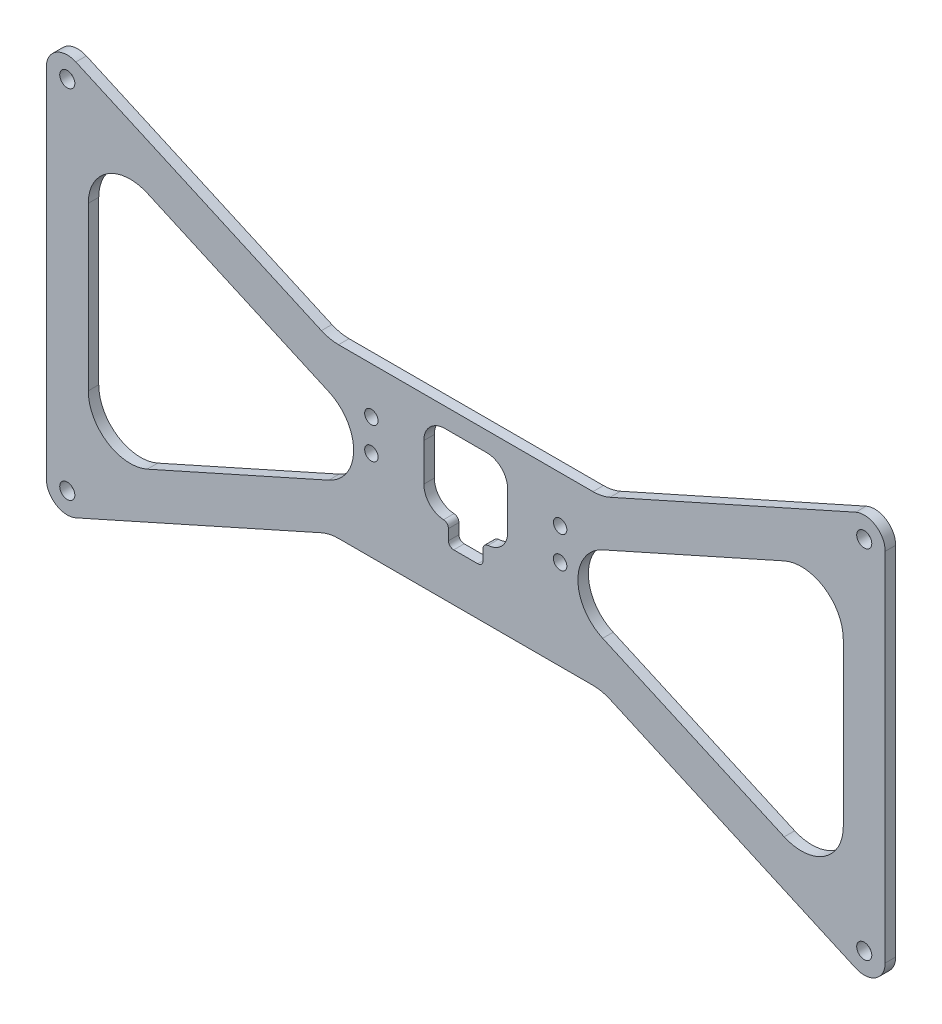
SolidWorks part; units mm, degrees
ref_plane "Front Plane" through (0, 0, 0) normal (0, 0, 1) x (1, 0, 0)
ref_plane "Top Plane" through (0, 0, 0) normal (0, 1, 0) x (1, 0, 0)
ref_plane "Right Plane" through (0, 0, 0) normal (1, 0, 0) x (0, 0, -1)
sketch "Sketch1" plane through (0, 0, 0) normal (0, 0, 1) x (1, 0, 0)
  line L0 (-120.65, -53.975) -> (120.65, 53.975) construction
  line L3 (-114.3, -44.1777) -> (-15.5498, 0)
  line L10 (-118.0569, -59.7714) -> (-41.2267, -25.4)
  line L11 (-120.65, 53.975) -> (120.65, -53.975) construction
  line L12 (-118.0569, 59.7714) -> (-41.2267, 25.4)
  line L13 (-114.3, 44.1777) -> (-15.5498, 0)
  line L14 (41.2267, 25.4) -> (118.0569, 59.7714)
  line L15 (41.2267, -25.4) -> (118.0569, -59.7714)
  line L16 (15.5498, 0) -> (114.3, 44.1777)
  line L17 (15.5498, 0) -> (114.3, -44.1777)
  line L18 (-127, 53.975) -> (-127, -53.975)
  line L19 (-114.3, 44.1777) -> (-114.3, -44.1777)
  line L20 (127, 53.975) -> (127, -53.975)
  line L21 (114.3, 44.1777) -> (114.3, -44.1777)
  line L24 (-41.2267, 25.4) -> (41.2267, 25.4)
  line L25 (-41.2267, -25.4) -> (41.2267, -25.4)
  arc A4 (-127, -53.975) -> (-118.0569, -59.7714) centre (-120.65, -53.975) ccw
  arc A5 (127, 53.975) -> (118.0569, 59.7714) centre (120.65, 53.975) ccw
  arc A6 (-118.0569, 59.7714) -> (-127, 53.975) centre (-120.65, 53.975) ccw
  arc A7 (118.0569, -59.7714) -> (127, -53.975) centre (120.65, -53.975) ccw
  point P2 (0, 0)
  point P9 (0, 0)
  point P13 (0, 0)
  point P26 (0, 0)
  dimension "D1" = 254
  dimension "D3" = 6.35
  dimension "D2" = 107.95
  dimension "D4" = 25.4
  dimension "D6" = 25.4
extrude "Boss-Extrude1" add sketch "Sketch1" along normal blind 3.175
sketch "Sketch2" plane through (0, 0, 3.175) normal (0, 0, 1) x (1, 0, 0)
  circle A0 centre (-120.65, 53.975) radius 2.286
  circle A1 centre (-120.65, -53.975) radius 2.286
  circle A2 centre (120.65, -53.975) radius 2.286
  circle A3 centre (120.65, 53.975) radius 2.286
  arc A4 (-118.0569, 59.7714) -> (-127, 53.975) centre (-120.65, 53.975) ccw construction
  arc A5 (-127, -53.975) -> (-118.0569, -59.7714) centre (-120.65, -53.975) ccw construction
  arc A6 (118.0569, -59.7714) -> (127, -53.975) centre (120.65, -53.975) ccw construction
  arc A7 (127, 53.975) -> (118.0569, 59.7714) centre (120.65, 53.975) ccw construction
  dimension "D1" = 4.572
extrude "Cut-Extrude1" cut sketch "Sketch2" against normal through all
fillet "Fillet1" radius 12.7 10 edges at (114.3, -44.1777, 1.5875) (114.3, 44.1777, 1.5875) (15.5498, 0, 1.5875) (-114.3, -44.1777, 1.5875) (-15.5498, 0, 1.5875) (-114.3, 44.1777, 1.5875) (-41.2267, 25.4, 1.5875) (41.2267, 25.4, 1.5875) (41.2267, -25.4, 1.5875) (-41.2267, -25.4, 1.5875)
sketch "Sketch9" plane through (0, 0, 3.175) normal (0, 0, 1) x (1, 0, 0)
  circle A0 centre (28.575, 11.4134) radius 2.032
  circle A1 centre (28.575, 1.8884) radius 2.032
  dimension "D1" = 4.064
extrude "Cut-Extrude6" cut sketch "Sketch9" against normal through all both and the other way through all
sketch "Sketch10" plane through (0, 0, 3.175) normal (0, 0, 1) x (1, 0, 0)
  line L0 (38.5154, 25.4) -> (-38.5154, 25.4) construction
  line L1 (-12.7, 19.5262) -> (12.7, 19.5262)
  line L2 (-12.7, 19.5262) -> (-12.7, -4.6037)
  line L3 (-12.7, -4.6037) -> (-5.2387, -4.6037)
  line L4 (12.7, 19.5262) -> (12.7, -4.6037)
  line L5 (-5.2387, -4.6037) -> (-5.2387, -10.9537)
  line L6 (-5.2387, -10.9537) -> (5.2387, -10.9537)
  line L7 (5.2387, -10.9537) -> (5.2387, -4.6037)
  line L8 (5.2387, -4.6037) -> (12.7, -4.6037)
  point P4 (0, 19.5262)
  point P11 (0, -10.9537)
  dimension "D1" = 25.4
  dimension "D2" = 24.13
  dimension "D3" = 5.8738
  dimension "D4" = 6.35
  dimension "D5" = 10.4775
extrude "Cut-Extrude7" cut sketch "Sketch10" against normal through all both and the other way through all
fillet "Fillet2" radius 6.35 4 edges at (-12.7, -4.6037, 1.5875) (12.7, -4.6037, 1.5875) (12.7, 19.5262, 1.5875) (-12.7, 19.5262, 1.5875)
fillet "Fillet3" radius 1.5875 4 edges at (-5.2387, -10.9537, 1.5875) (5.2387, -10.9537, 1.5875) (5.2387, -4.6037, 1.5875) (-5.2388, -4.6037, 1.5875)
mirror "Mirror1" about plane through (0, 0, 0) normal (1, 0, 0) of "Cut-Extrude6"
